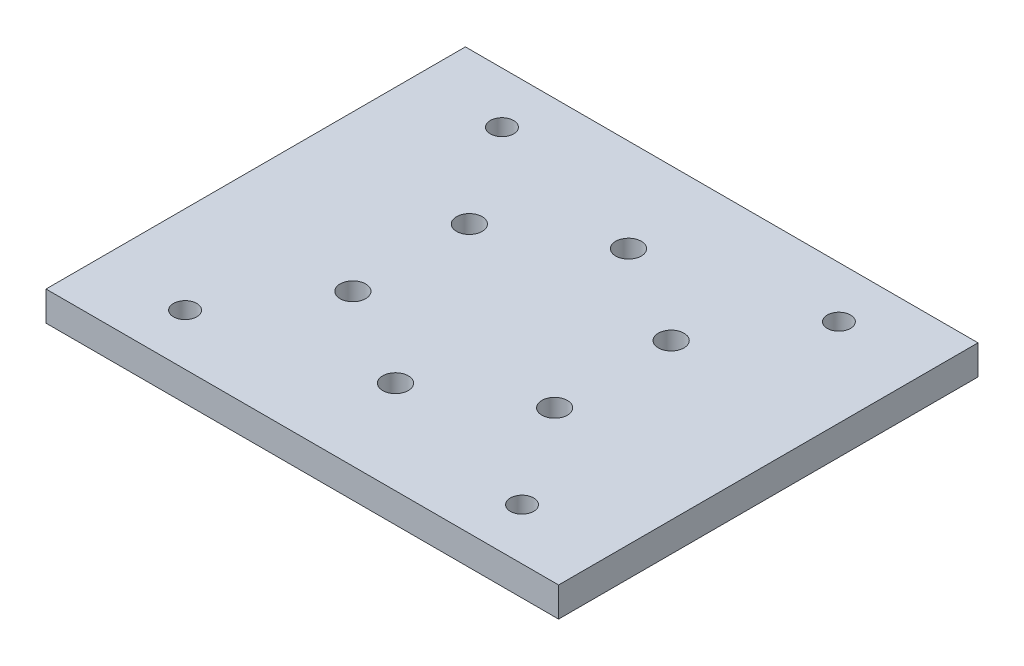
SolidWorks part; units mm, degrees
ref_plane "Front Plane" through (0, 0, 0) normal (0, 0, 1) x (1, 0, 0)
ref_plane "Top Plane" through (0, 0, 0) normal (0, 1, 0) x (1, 0, 0)
ref_plane "Right Plane" through (0, 0, 0) normal (1, 0, 0) x (0, 0, -1)
sketch "Sketch2" plane through (0, 0, 0) normal (0, 1, 0) x (1, 0, 0)
  line L0 (0, 0) -> (0, 90)
  line L1 (0, 90) -> (110, 90)
  line L2 (110, 90) -> (110, 0)
  line L3 (110, 0) -> (0, 0)
  dimension "D1" = 110
  dimension "D2" = 90
extrude "Boss-Extrude1" add sketch "Sketch2" along normal blind 6.35
sketch "Sketch3" plane through (0, 6.35, 0) normal (0, 1, 0) x (1, 0, 0)
  line L1 (110, 90) -> (0, 90) construction
  line L2 (0, 0) -> (110, 0) construction
  line L4 (55, 90) -> (55, 0) construction
  line L5 (0, 45) -> (55, 45) construction
  line L6 (55, 45) -> (110, 45) construction
  line L7 (0, 90) -> (0, 0) construction
  circle A0 centre (18.85, 79) radius 2.5
  circle A1 centre (18.85, 11) radius 2.5
  circle A2 centre (91.15, 11) radius 2.5
  circle A3 centre (91.15, 79) radius 2.5
  point P0 (0, 0)
  dimension "D4" = 5
  dimension "D3" = 11
  dimension "D2" = 18.85
extrude "Mounting Holes" cut sketch "Sketch3" against normal through all
sketch "Sketch4" plane through (0, 6.35, 0) normal (0, 1, 0) x (1, 0, 0)
  line L0 (18.85, 79) -> (91.15, 11) construction
  circle A0 centre (55, 45) radius 25 construction
  circle A1 centre (55, 70) radius 2.75
  circle A2 centre (76.6506, 57.5) radius 2.75
  circle A3 centre (76.6506, 32.5) radius 2.75
  circle A4 centre (55, 20) radius 2.75
  circle A5 centre (33.3494, 32.5) radius 2.75
  circle A6 centre (33.3494, 57.5) radius 2.75
  point P20 (55, 45)
  dimension "D1" = 50
  dimension "D2" = 5.5
  dimension "D3" = 6
extrude "Cut-Extrude1" cut sketch "Sketch4" against normal through all
sketch "Sketch5" plane through (0, 6.35, 0) normal (0, 1, 0) x (1, 0, 0)
  circle A0 centre (55, 45) radius 25 construction
  circle A1 centre (55, 20) radius 2.75 construction
  circle A2 centre (55, 20) radius 2.75 construction
  circle A3 centre (33.3494, 32.5) radius 2.75 construction
  circle A4 centre (33.3494, 32.5) radius 2.75 construction
  circle A5 centre (33.3494, 57.5) radius 2.75 construction
  circle A6 centre (33.3494, 57.5) radius 2.75 construction
equation "\"L1L\"=500"
equation "\"L1Thick\"=6.35"
equation "\"Harm-Drive-Outer\"=74.5"
equation "\"L1-Spacing\"=100"
equation "\"L-Bracket-HoleToWall\"=12.5"
equation "\"D3@Sketch3\"=\"L-Bracket-HoleToSide\""
equation "\"L-Bracket-HoleToSide\"=11"
equation "\"Bracket-Hole-D\"=6.8"
equation "\"L1-Spacing\"=115.65"
equation "\"D2@Sketch3\"=\"L-Bracket-HoleToWall\"+\"L1Thick\""
